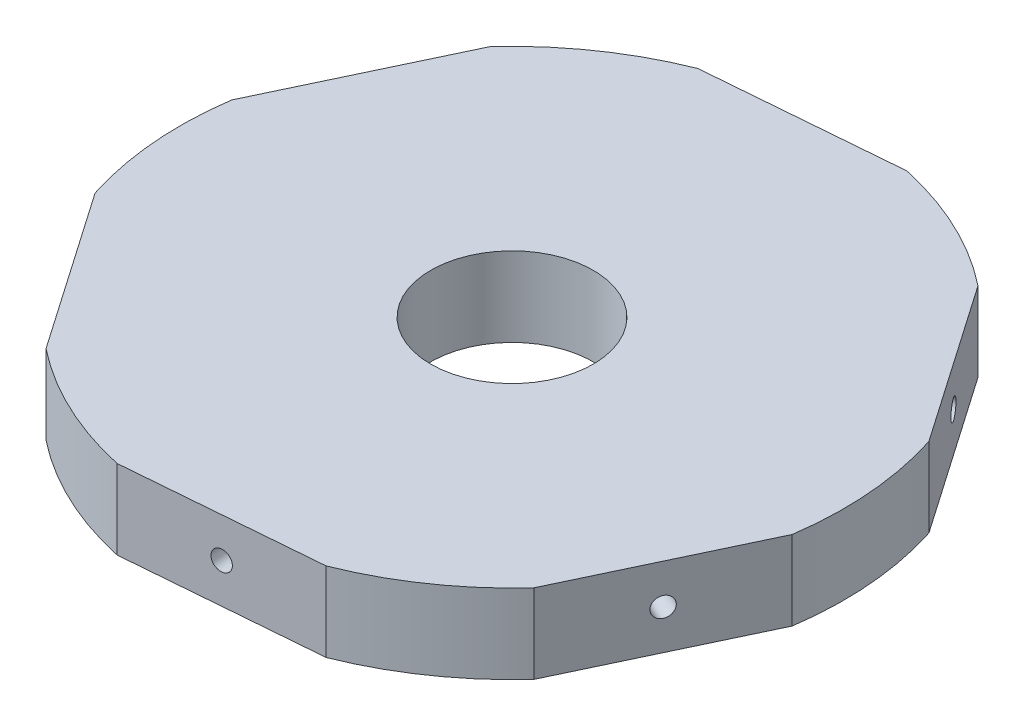
SolidWorks part; units mm, degrees
ref_plane "Front Plane" through (0, 0, 0) normal (0, 0, 1) x (1, 0, 0)
ref_plane "Top Plane" through (0, 0, 0) normal (0, 1, 0) x (1, 0, 0)
ref_plane "Right Plane" through (0, 0, 0) normal (1, 0, 0) x (0, 0, -1)
sketch "Sketch2" plane through (0, 0, 0) normal (0, 1, 0) x (1, 0, 0)
  line L1 (17.8375, 81.7283) -> (-30.8946, 77.7381)
  line L2 (-61.86, 56.3118) -> (-82.7704, 12.1135)
  line L3 (-79.6975, -25.4164) -> (-51.8759, -65.6245)
  line L4 (-17.8375, -81.7283) -> (30.8946, -77.7381)
  line L5 (61.86, -56.3118) -> (82.7704, -12.1135)
  line L6 (79.6975, 25.4164) -> (51.8759, 65.6245)
  arc A0 (-82.7704, 12.1135) -> (-79.6975, -25.4164) centre (0, 0) ccw
  circle A1 centre (0, 0) radius 80 construction
  arc A2 (-30.8946, 77.7381) -> (-61.86, 56.3118) centre (0, 0) ccw
  arc A3 (51.8759, 65.6245) -> (17.8375, 81.7283) centre (0, 0) ccw
  arc A4 (82.7704, -12.1135) -> (79.6975, 25.4164) centre (0, 0) ccw
  arc A5 (30.8946, -77.7381) -> (61.86, -56.3118) centre (0, 0) ccw
  arc A6 (-51.8759, -65.6245) -> (-17.8375, -81.7283) centre (0, 0) ccw
  circle A7 centre (0, 0) radius 20.5
  dimension "D1" = 160
extrude "Boss-Extrude1" add sketch "Sketch2" along normal blind 20
sketch "Sketch3" plane through (6.5285, 0, 79.7332) normal (0.0816, 0, 0.9967) x (0.9967, 0, -0.0816)
  line L0 (-24.4476, 0) -> (24.4476, 0) construction
  circle A0 centre (0, 10) radius 2.5
  dimension "D1" = 5
  dimension "D2" = 10
extrude "Cut-Extrude1" cut sketch "Sketch3" against normal blind 20
pattern_circular "CirPattern1" count 6 over 360 about axis through (0, 20, 0) along (0, 1, 0) of "Cut-Extrude1"
